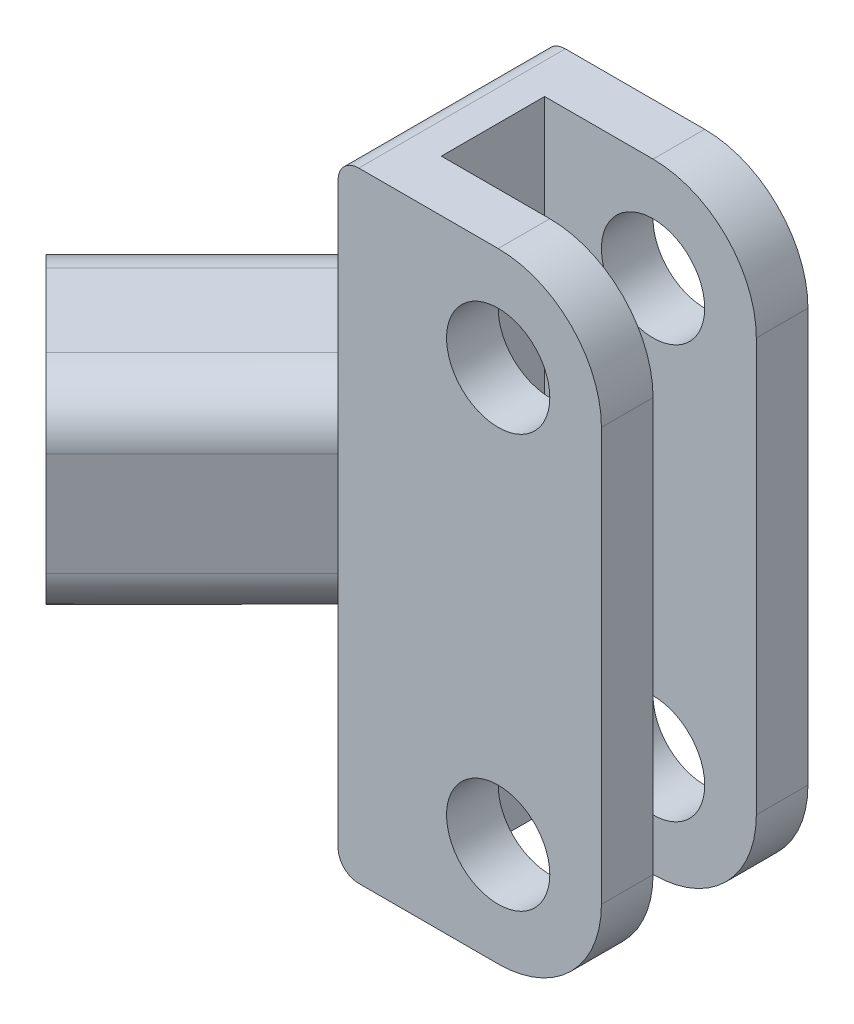
SolidWorks part; units mm, degrees
ref_plane "Front Plane" through (0, 0, 0) normal (0, 0, 1) x (1, 0, 0)
ref_plane "Top Plane" through (0, 0, 0) normal (0, 1, 0) x (1, 0, 0)
ref_plane "Right Plane" through (0, 0, 0) normal (1, 0, 0) x (0, 0, -1)
ref_axis "X" through (-88.99, 0, 0) along (1, 0, 0)
ref_axis "Y" through (0, 55, 0) along (0, -1, 0)
ref_axis "Z" through (0, 0, -88.99) along (0, 0, 1)
sketch "Sketch1" plane through (0, 0, 0) normal (0, 0, 1) x (1, 0, 0)
  line L0 (0, 20) -> (0, -20) construction
  line L1 (-10.5, 30) -> (0, 30)
  line L2 (10, 20) -> (10, -20)
  line L3 (0, -30) -> (-10.5, -30)
  line L4 (-10.5, 30) -> (-10.5, -30)
  line L5 (-10.5, 30) -> (-15.5, 30)
  line L6 (-15.5, 30) -> (-15.5, -30)
  line L7 (-15.5, -30) -> (-10.5, -30)
  circle A0 centre (0, 20) radius 5
  circle A1 centre (0, -20) radius 5
  arc A2 (0, 30) -> (10, 20) centre (0, 20) cw
  arc A3 (10, -20) -> (0, -30) centre (0, -20) cw
  point P4 (0, 0)
  dimension "D1" = 40
  dimension "D2" = 10
  dimension "D3" = 5
  dimension "D4" = 10.5
  dimension "D5" = 5
extrude "Boss-Extrude1" add sketch "Sketch1" along normal mid plane 10 contours L6 L7 L4 L5 region at (-13, 0, 0)
extrude "Boss-Extrude2" add sketch "Sketch1<3>" along normal blind 5 from surface contours L6 L7 L4 L5 | A3 L2 A2 L1 L4 L3 A0 A1 region at (-0.6222, 0, 0) region at (-13, 0, 0) starting at face at (-13, 0, 5)
sketch "Sketch1<3>" plane through (0, 0, 0) normal (0, 0, 1) x (1, 0, 0) same geometry as "Sketch1"
extrude "Boss-Extrude3" add sketch "Sketch1<4>" against normal blind 5 from surface contours A3 L2 A2 L1 L4 L3 A0 A1 | L6 L7 L4 L5 region at (-0.6222, 0, 0) region at (-13, 0, 0) starting at face at (-13, 0, -5)
sketch "Sketch1<4>" plane through (0, 0, 0) normal (0, 0, 1) x (1, 0, 0) same geometry as "Sketch1"
sketch "Sketch3" plane through (0, 0, 0) normal (0, 1, 0) x (1, 0, 0)
  line L0 (-15.5, -10) -> (-15.5, 10) construction
  line L1 (-15.5, -10) -> (-15.5, 10)
  line L2 (-15.5, -10) -> (-29.6421, -24.1421)
  line L3 (-29.6421, -24.1421) -> (-43.7843, -10)
  line L5 (-29.6421, 4.1421) -> (-43.7843, -10)
  line L6 (-15.5, 10) -> (-12.0739, 10) construction
  arc A0 (-15.5, 10) -> (-29.6421, 4.1421) centre (-15.5, -10) ccw
  point P6 (-24.651, 5.0669)
  dimension "D1" = 20
  dimension "D2" = 20
  dimension "D3" = 45
extrude "Boss-Extrude4" add sketch "Sketch3" along normal mid plane 20
fillet "Fillet3" radius 5 6 edges at (-23.1537, -10, -8.4776) (-23.1537, 10, -8.4776) (-22.5711, -10, 17.0711) (-22.5711, 10, 17.0711) (-36.7132, -10, 2.9289) (-36.7132, 10, 2.9289)
fillet "Fillet2" radius 2 2 edges at (-15.5, -30, 0) (-15.5, 30, 0)
sketch "Sketch4" plane through (-26.8921, 0, 26.8921) normal (-0.7071, 0, 0.7071) x (0.7071, 0, 0.7071)
  line L4 (-23.8891, 0) -> (-3.8891, 0) construction
  line L8 (-18.8891, -10) -> (-8.8891, -10)
  line L9 (-3.8891, -5) -> (-3.8891, 5)
  line L10 (-8.8891, 10) -> (-18.8891, 10)
  line L11 (-23.8891, 5) -> (-23.8891, -5)
  line L12 (-18.8891, -10) -> (-8.8891, -10)
  line L13 (-3.8891, -5) -> (-3.8891, 5)
  line L14 (-8.8891, 10) -> (-18.8891, 10)
  line L15 (-23.8891, 5) -> (-23.8891, -5)
  circle A4 centre (-13.8891, 0) radius 7.5
  arc A8 (-8.8891, -10) -> (-3.8891, -5) centre (-8.8891, -5) ccw
  arc A9 (-3.8891, 5) -> (-8.8891, 10) centre (-8.8891, 5) ccw
  arc A10 (-18.8891, 10) -> (-23.8891, 5) centre (-18.8891, 5) ccw
  arc A11 (-23.8891, -5) -> (-18.8891, -10) centre (-18.8891, -5) ccw
  arc A12 (-8.8891, -10) -> (-3.8891, -5) centre (-8.8891, -5) ccw
  arc A13 (-3.8891, 5) -> (-8.8891, 10) centre (-8.8891, 5) ccw
  arc A14 (-18.8891, 10) -> (-23.8891, 5) centre (-18.8891, 5) ccw
  arc A15 (-23.8891, -5) -> (-18.8891, -10) centre (-18.8891, -5) ccw
  dimension "D2" = 15
  dimension "D1" = 0
extrude "Cut-Extrude1" cut sketch "Sketch4" against normal blind 15 contours A4 L4 | L4 A4 region at (-36.7132, -3.1831, 17.0711) region at (-36.7132, 3.1831, 17.0711)
